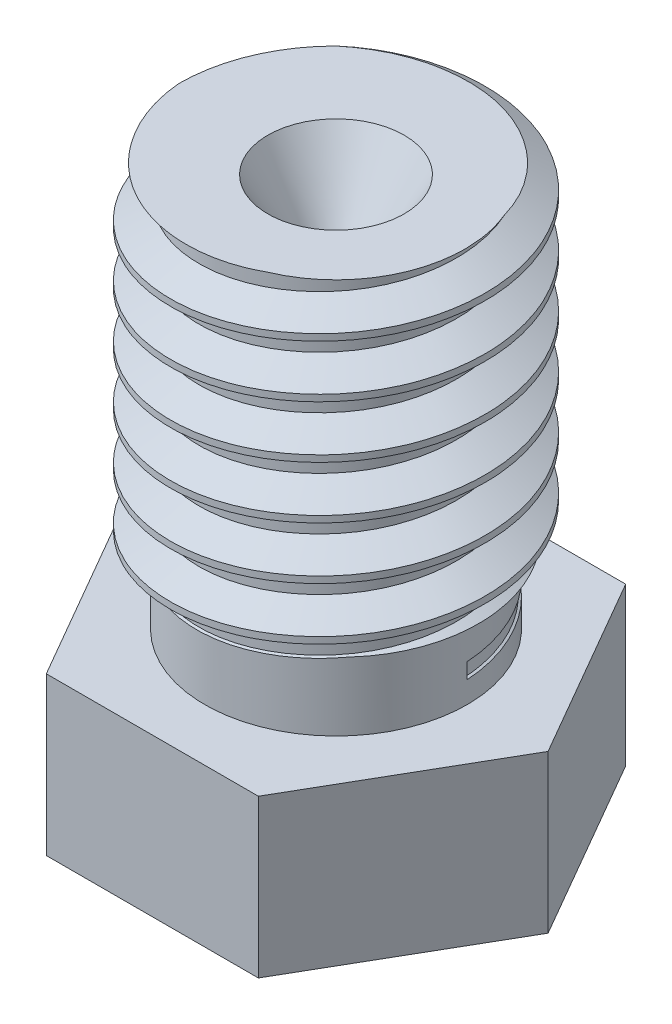
SolidWorks part; units mm, degrees
material "Bronce de aluminio"
ref_plane "Alzado" through (0, 0, 0) normal (0, 0, 1) x (1, 0, 0)
ref_plane "Planta" through (0, 0, 0) normal (0, 1, 0) x (1, 0, 0)
ref_plane "Vista lateral" through (0, 0, 0) normal (1, 0, 0) x (0, 0, -1)
sketch "Croquis1" plane through (0, 0, 0) normal (0, 0, 1) x (1, 0, 0)
  line L0 (0, 0) -> (0, 30) construction
  line L1 (0.2, 0.6) -> (0.2, 0)
  line L2 (0.2, 0) -> (0.5, 0)
  line L3 (0.5, 0) -> (1.6547, 2)
  line L4 (1.6547, 2) -> (3.5, 2)
  line L5 (3.5, 2) -> (3.5, 5)
  line L6 (3.5, 5) -> (2.5, 5)
  line L7 (2.5, 5) -> (2.5, 6.3)
  line L8 (2.5, 6.3) -> (3, 6.5)
  line L9 (3, 6.5) -> (3, 12.5)
  line L10 (3, 12.5) -> (1.3, 12.5)
  line L11 (1.3, 12.5) -> (0.5, 11.1144)
  line L12 (0.5, 11.1144) -> (0.5, 1.1196)
  line L13 (0.5, 1.1196) -> (0.2, 0.6)
  dimension "D1" = 30
  dimension "D2" = 0.2
  dimension "D3" = 0.5
  dimension "D4" = 0.6
  dimension "D5" = 30
  dimension "D6" = 1.3
  dimension "D7" = 2.5
  dimension "D8" = 3.5
  dimension "D9" = 7.5
  dimension "D10" = 6
  dimension "D11" = 1
  dimension "D12" = 12.5
  dimension "D13" = 10.5
  dimension "D14" = 3
  dimension "D15" = 0.2
revolve "Revolución1" add sketch "Croquis1" angle 360 about L0
sketch "Croquis2" plane through (0, 2, 0) normal (0, -1, 0) x (1, 0, 0)
  line L1 (4.0415, 0) -> (2.0207, 3.5)
  line L2 (2.0207, 3.5) -> (-2.0207, 3.5)
  line L3 (-2.0207, 3.5) -> (-4.0415, 0)
  line L4 (-4.0415, 0) -> (-2.0207, -3.5)
  line L5 (-2.0207, -3.5) -> (2.0207, -3.5)
  line L6 (2.0207, -3.5) -> (4.0415, 0)
  circle A0 centre (0, 0) radius 3.5 construction
  circle A2 centre (0, 0) radius 2.5
  dimension "D2" = 5
  dimension "D1" = 7
extrude "Saliente-Extruir2" add sketch "Croquis2" against normal up to surface (3 mm away) up to face at (0, 5, -2.5)
thread "Rosca1" pitch 1 start angle 0, offset 1, length 0, pitch 1, diameter 6
ref_plane "Plano1" through (-3, 13.5, 0) normal (0, 0, 1) x (-1, 0, 0)
sketch "Perfil de rosca1" plane through (-3, 13.5, 0) normal (0, 0, 1) x (-1, 0, 0)
  line L0 (0, 0) -> (0, 1) construction
  line L11 (0, 0) -> (0, 0.875)
  line L12 (0, 0.875) -> (-0.5413, 0.5625)
  line L13 (-0.5413, 0.5625) -> (-0.5413, 0.3125)
  line L15 (-0.5413, 0.3125) -> (0, 0)
  line L17 (-0.5413, 0.4375) -> (0, 0.4375) construction
  point P2 (0, 0)
  dimension "Pitch" = 1
  dimension "Profile_Angle" = 60
  dimension "Profile_Land" = 0.25
  dimension "Profile_Height" = 0.5413
